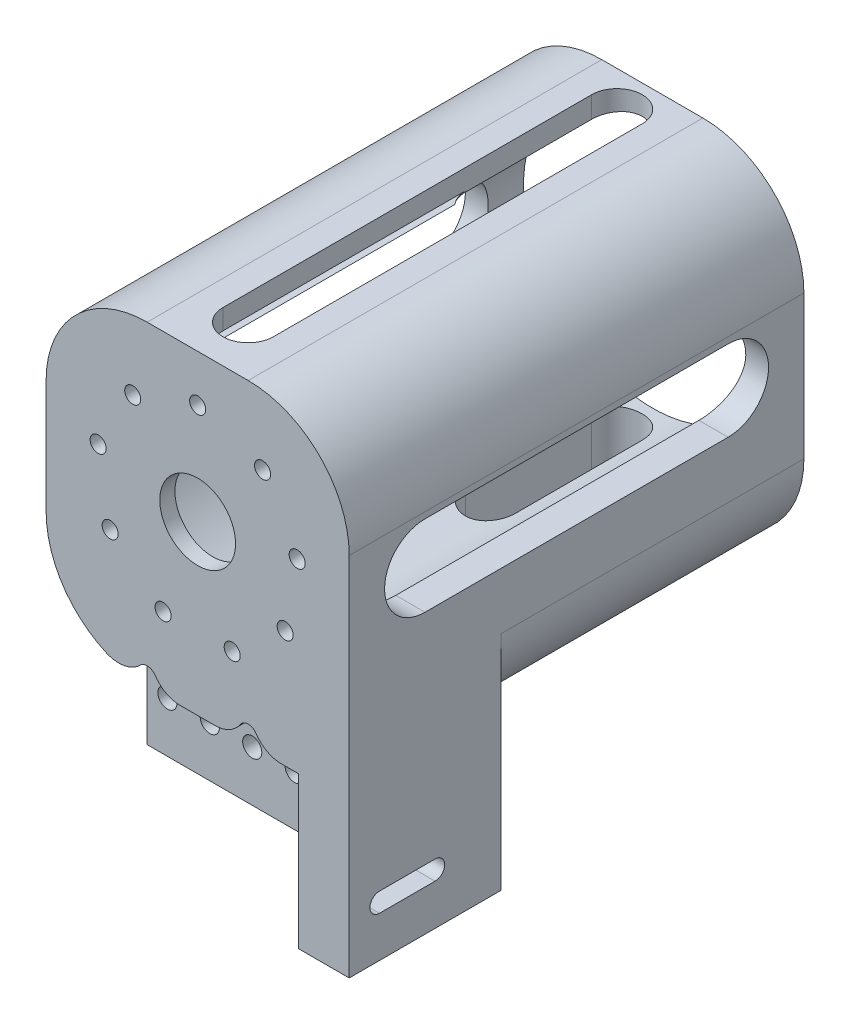
SolidWorks part; units mm, degrees
ref_plane "Front Plane" through (0, 0, 0) normal (0, 0, 1) x (1, 0, 0)
ref_plane "Top Plane" through (0, 0, 0) normal (0, 1, 0) x (1, 0, 0)
ref_plane "Right Plane" through (0, 0, 0) normal (1, 0, 0) x (0, 0, -1)
sketch "Sketch1" plane through (0, 0, 0) normal (0, 0, 1) x (1, 0, 0)
  line L0 (-38.1, 37.1192) -> (-38.1, -80.264)
  line L1 (-38.1, -80.264) -> (38.1, -80.264)
  line L2 (38.1, -80.264) -> (38.1, 37.1192)
  line L3 (38.1, 37.1192) -> (-38.1, 37.1192)
  line L4 (0, 37.1192) -> (0, -80.264) construction
  circle A0 centre (0, 0) radius 9.525
  circle A1 centre (0, 0) radius 32.385 construction
  dimension "D1" = 19.05
  dimension "D4" = 64.77
  dimension "D3" = 76.2
  dimension "D5" = 80.264
extrude "Boss-Extrude1" add sketch "Sketch1" along normal blind 3.81
sketch "Sketch2" plane through (0, 0, 0) normal (0, 0, -1) x (-1, 0, 0)
  line L0 (38.1, -80.264) -> (-38.1, -80.264) construction
  line L1 (-38.1, 37.1192) -> (38.1, 37.1192)
  line L2 (-38.1, 37.1192) -> (-38.1, -80.264)
  line L3 (-38.1, -80.264) -> (38.1, -80.264)
  line L4 (38.1, 37.1192) -> (38.1, -80.264)
  line L5 (-38.1, 37.1192) -> (38.1, 37.1192) construction
  line L6 (0, -80.264) -> (0, -32.385) construction
  circle A0 centre (0, 0) radius 32.385
  dimension "D1" = 64.77
  dimension "D2" = 38.1
  dimension "D3" = 38.1
extrude "Boss-Extrude2" add sketch "Sketch2" along normal blind 34.29
sketch "Sketch3" plane through (0, 0, -34.29) normal (0, 0, -1) x (-1, 0, 0)
  line L0 (38.1, -80.264) -> (38.1, 37.1192) construction
  line L1 (-38.1, 37.1192) -> (38.1, 37.1192)
  line L2 (-38.1, 37.1192) -> (-38.1, -49.784)
  line L3 (-38.1, -49.784) -> (38.1, -49.784)
  line L4 (38.1, 37.1192) -> (38.1, -49.784)
  line L5 (-38.1, -80.264) -> (38.1, -80.264) construction
  circle A0 centre (0, 0) radius 32.385
  dimension "D1" = 30.48
extrude "Boss-Extrude3" add sketch "Sketch3" along normal blind 76.2
fillet "Fillet2" radius 25.4 4 edges at (38.1, 37.1192, -53.34) (-38.1, 37.1192, -53.34)
sketch "Sketch4" plane through (0, -80.264, 0) normal (0, -1, 0) x (-1, 0, 0)
  line L0 (-38.1, -3.81) -> (-38.1, 34.29) construction
  line L1 (38.1, -3.81) -> (-25.4, -3.81)
  line L2 (38.1, -3.81) -> (38.1, 21.59)
  line L3 (38.1, 21.59) -> (-25.4, 21.59)
  line L4 (-25.4, -3.81) -> (-25.4, 21.59)
  line L5 (-38.1, 34.29) -> (38.1, 34.29) construction
  dimension "D1" = 12.7
  dimension "D2" = 12.7
extrude "Cut-Extrude1" cut sketch "Sketch4" against normal blind 38.1
fillet "Fillet3" radius 25.4 1 edges at (-38.1, -42.164, -8.89)
sketch "Sketch5" plane through (0, 0, -110.49) normal (0, 0, -1) x (-1, 0, 0)
  line L0 (-12.7, -40.103) -> (12.7, -40.103) construction
  line L1 (-12.7, -49.784) -> (12.7, -49.784) construction
  line L2 (0, 0) -> (0, -40.103) construction
  circle A0 centre (-12.7, -40.103) radius 2.413
  circle A1 centre (12.7, -40.103) radius 2.413
  circle A2 centre (-12.7, -40.103) radius 9.681 construction
  circle A3 centre (0, 0) radius 32.385 construction
  arc A6 (-38.1, -24.384) -> (-12.7, -49.784) centre (-12.7, -24.384) ccw construction
  dimension "D1" = 4.826
extrude "Cut-Extrude2" cut sketch "Sketch5" against normal through all
fillet "Fillet4" radius 7.62 4 edges at (13.955, -42.164, -8.89) (11.445, -42.164, -8.89) (-14.0088, -42.1303, -8.89) (-11.445, -42.164, -8.89)
sketch "Sketch6" plane through (0, 0, -34.29) normal (0, 0, -1) x (-1, 0, 0)
  line L0 (-38.1, -67.564) -> (38.1, -67.564) construction
  line L1 (-38.1, -24.384) -> (-38.1, -80.264) construction
  line L2 (38.1, -80.264) -> (38.1, -24.384) construction
  line L3 (-38.1, -80.264) -> (38.1, -80.264) construction
  line L4 (-25.4, -80.264) -> (-25.4, -54.864) construction
  line L5 (-25.4, -42.164) -> (-25.4, -80.264) construction
  line L6 (-25.4, -54.864) -> (-20.32, -67.564) construction
  line L8 (38.1, -54.864) -> (33.02, -67.564) construction
  circle A0 centre (33.02, -67.564) radius 2.413
  circle A1 centre (22.352, -67.564) radius 2.413
  circle A2 centre (11.684, -67.564) radius 2.413
  circle A3 centre (1.016, -67.564) radius 2.413
  circle A4 centre (-9.652, -67.564) radius 2.413
  circle A5 centre (-20.32, -67.564) radius 2.413
  dimension "D2" = 6
  dimension "D5" = 4.826
  dimension "D1" = 12.7
  dimension "D3" = 25.4
  dimension "D4" = 5.08
extrude "Cut-Extrude3" cut sketch "Sketch6" against normal through all
sketch "Sketch7" plane through (38.1, 0, 0) normal (1, 0, 0) x (0, 0, -1)
  line L0 (15.24, 0) -> (91.44, 0) construction
  line L1 (15.24, 10.16) -> (91.44, 10.16)
  line L2 (15.24, -10.16) -> (91.44, -10.16)
  line L3 (-3.81, -80.264) -> (-3.81, 11.7192) construction
  line L4 (110.49, 11.7192) -> (110.49, -24.384) construction
  arc A0 (15.24, 10.16) -> (15.24, -10.16) centre (15.24, 0) ccw
  arc A1 (91.44, -10.16) -> (91.44, 10.16) centre (91.44, 0) ccw
  point P3 (53.34, 0)
  dimension "D3" = 10.16
  dimension "D1" = 19.05
  dimension "D2" = 19.05
extrude "Cut-Extrude4" cut sketch "Sketch7" against normal through all
sketch "Sketch8" plane through (0, -49.784, 0) normal (0, -1, 0) x (-1, 0, 0)
  line L0 (12.7, 34.29) -> (12.7, 110.49) construction
  line L1 (12.7, 53.34) -> (-12.7, 53.34)
  line L2 (12.7, 53.34) -> (12.7, 58.42)
  line L3 (12.7, 58.42) -> (-12.7, 58.42)
  line L4 (-12.7, 53.34) -> (-12.7, 58.42)
  line L5 (-12.7, 110.49) -> (-12.7, 34.29) construction
  line L6 (0, 58.42) -> (0, 110.49) construction
  line L7 (-12.7, 110.49) -> (12.7, 110.49) construction
  line L8 (0, 53.34) -> (0, 34.29) construction
  line L9 (-12.7, 34.29) -> (12.7, 34.29) construction
  dimension "D1" = 5.08
  dimension "D2" = 19.05
extrude "Boss-Extrude4" add sketch "Sketch8" along normal blind 5.08
fillet "Fillet5" radius 5.08 2 edges at (0, -49.784, -58.42) (0, -49.784, -53.34)
sketch "Sketch9" plane through (38.1, 0, 0) normal (1, 0, 0) x (0, 0, -1)
  line L0 (3.81, -67.564) -> (17.78, -67.564) construction
  line L1 (3.81, -65.151) -> (17.78, -65.151)
  line L2 (3.81, -69.977) -> (17.78, -69.977)
  line L3 (-3.81, -80.264) -> (34.29, -80.264) construction
  line L4 (-3.81, -80.264) -> (-3.81, 11.7192) construction
  line L5 (34.29, -24.384) -> (34.29, -80.264) construction
  arc A0 (3.81, -65.151) -> (3.81, -69.977) centre (3.81, -67.564) ccw
  arc A1 (17.78, -69.977) -> (17.78, -65.151) centre (17.78, -67.564) ccw
  point P2 (10.795, -67.564)
  dimension "D2" = 2.413
  dimension "D1" = 12.7
  dimension "D3" = 7.62
  dimension "D4" = 16.51
extrude "Cut-Extrude7" cut sketch "Sketch9" against normal through all
sketch "Sketch10" plane through (0, -49.784, 0) normal (0, -1, 0) x (1, 0, 0)
  line L0 (0, -101.6) -> (0, -69.85) construction
  line L1 (-6.35, -101.6) -> (-6.35, -69.85)
  line L2 (6.35, -101.6) -> (6.35, -69.85)
  line L3 (12.7, -63.5) -> (-12.7, -63.5) construction
  line L4 (12.7, -110.49) -> (-12.7, -110.49) construction
  arc A0 (-6.35, -101.6) -> (6.35, -101.6) centre (0, -101.6) ccw
  arc A1 (6.35, -69.85) -> (-6.35, -69.85) centre (0, -69.85) ccw
  point P3 (0, -85.725)
  dimension "D3" = 6.35
  dimension "D1" = 6.35
  dimension "D2" = 8.89
extrude "Cut-Extrude8" cut sketch "Sketch10" against normal through all
sketch "Sketch11" plane through (0, 37.1192, 0) normal (0, 1, 0) x (1, 0, 0)
  line L0 (0, 8.89) -> (0, 101.6) construction
  line L1 (-6.35, 8.89) -> (-6.35, 101.6)
  line L2 (6.35, 8.89) -> (6.35, 101.6)
  line L3 (12.7, -3.81) -> (-12.7, -3.81) construction
  line L4 (-6.35, 69.85) -> (-6.35, 101.6) construction
  line L5 (6.35, 101.6) -> (6.35, 69.85) construction
  arc A0 (-6.35, 8.89) -> (6.35, 8.89) centre (0, 8.89) ccw
  arc A1 (6.35, 101.6) -> (-6.35, 101.6) centre (0, 101.6) ccw
  arc A2 (6.35, 101.6) -> (-6.35, 101.6) centre (0, 101.6) ccw construction
  point P3 (0, 55.245)
  point P8 (0, -3.81)
  dimension "D1" = 12.7
extrude "Cut-Extrude9" cut sketch "Sketch11" against normal blind 5.08
sketch "Sketch12" plane through (0, 0, 3.81) normal (0, 0, 1) x (1, 0, 0)
  circle A0 centre (0, 0) radius 25.4 construction
  circle A1 centre (0, 25.4) radius 2.0193
  circle A2 centre (16.3268, 19.4575) radius 2.0193
  circle A3 centre (25.0141, 4.4107) radius 2.0193
  circle A4 centre (21.997, -12.7) radius 2.0193
  circle A5 centre (8.6873, -23.8682) radius 2.0193
  circle A6 centre (-8.6873, -23.8682) radius 2.0193
  circle A7 centre (-21.997, -12.7) radius 2.0193
  circle A8 centre (-25.0141, 4.4107) radius 2.0193
  circle A9 centre (-16.3268, 19.4575) radius 2.0193
  point P23 (0, 0)
  dimension "D1" = 50.8
  dimension "D2" = 4.0386
  dimension "D3" = 9
extrude "Cut-Extrude10" cut sketch "Sketch12" against normal blind 5.08
sketch "Sketch13" plane through (0, 0, -110.49) normal (0, 0, -1) x (-1, 0, 0)
  line L0 (-17.3786, 31.75) -> (17.3786, -31.75) construction
  line L1 (-31.75, -17.3786) -> (31.75, 17.3786) construction
  line L2 (-31.75, 17.3786) -> (31.75, -17.3786) construction
  line L3 (-17.3786, -31.75) -> (17.3786, 31.75) construction
  line L4 (-31.75, -17.3786) -> (31.75, -17.3786) construction
  line L5 (-17.3786, -31.75) -> (17.3786, -31.75) construction
  line L6 (-31.75, 17.3786) -> (-28.4079, 15.5493)
  line L7 (-17.3786, 31.75) -> (-15.5493, 28.4079)
  line L8 (17.3786, 31.75) -> (15.5493, 28.4079)
  line L9 (31.75, 17.3786) -> (28.4079, 15.5493)
  line L10 (31.75, -17.3786) -> (28.4079, -15.5493)
  line L11 (17.3786, -31.75) -> (15.5493, -28.4079)
  line L12 (-17.3786, -31.75) -> (-15.5493, -28.4079)
  line L13 (-31.75, -17.3786) -> (-28.4079, -15.5493)
  line L14 (-31.75, 17.3786) -> (-31.75, -17.3786) construction
  line L15 (-38.1, 11.7192) -> (-38.1, -24.384) construction
  arc A0 (-15.5493, -28.4079) -> (-28.4079, -15.5493) centre (0, 0) cw
  circle A1 centre (0, 0) radius 32.385 construction
  arc A2 (-28.4079, 15.5493) -> (-15.5493, 28.4079) centre (0, 0) cw
  arc A3 (15.5493, 28.4079) -> (28.4079, 15.5493) centre (0, 0) cw
  arc A4 (28.4079, -15.5493) -> (15.5493, -28.4079) centre (0, 0) cw
  arc A5 (-31.75, -17.3786) -> (-17.3786, -31.75) centre (0, 0) ccw
  arc A6 (-31.75, 17.3786) -> (-17.3786, 31.75) centre (0, 0) cw
  arc A7 (17.3786, 31.75) -> (31.75, 17.3786) centre (0, 0) cw
  arc A8 (31.75, -17.3786) -> (17.3786, -31.75) centre (0, 0) cw
  dimension "D1" = 3.81
  dimension "D2" = 6.35
extrude "Cut-Extrude12" cut sketch "Sketch13" against normal blind 101.6
